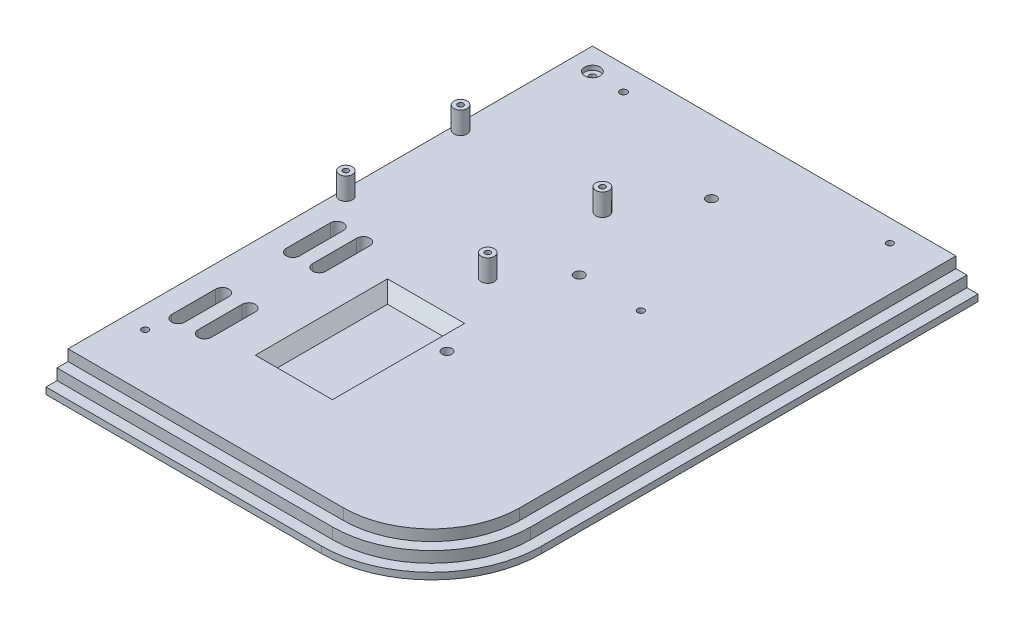
SolidWorks part; units mm, degrees
material "PETG"
ref_plane "Alzado" through (0, 0, 0) normal (0, 0, 1) x (1, 0, 0)
ref_plane "Planta" through (0, 0, 0) normal (0, 1, 0) x (1, 0, 0)
ref_plane "Vista lateral" through (0, 0, 0) normal (1, 0, 0) x (0, 0, -1)
sketch "Croquis1" plane through (0, 0, 0) normal (0, 1, 0) x (1, 0, 0)
  line L1 (125, 225) -> (-125, 225)
  line L2 (175, 175) -> (175, -175)
  line L3 (125, -225) -> (-125, -225)
  line L4 (-175, 175) -> (-175, -175)
  line L5 (175, 225) -> (-175, -225) construction
  line L6 (175, -225) -> (-175, 225) construction
  arc A0 (-125, -225) -> (-175, -175) centre (-125, -175) cw
  arc A1 (175, -175) -> (125, -225) centre (125, -175) cw
  arc A2 (125, 225) -> (175, 175) centre (125, 175) cw
  arc A3 (-125, 225) -> (-175, 175) centre (-125, 175) ccw
  point P0 (0, 0)
  dimension "D3" = 50
  dimension "D1" = 450
  dimension "D2" = 350
extrude "Saliente-Extruir1" add sketch "Croquis1" along normal blind 3
sketch "Croquis2" plane through (0, 3, 0) normal (0, 1, 0) x (1, 0, 0)
  line L8 (-125, -220) -> (125, -220)
  line L9 (170, -175) -> (170, 175)
  line L10 (125, 220) -> (-125, 220)
  line L11 (-170, 175) -> (-170, -175)
  line L12 (-125, -220) -> (125, -220)
  line L13 (170, -175) -> (170, 175)
  line L14 (125, 220) -> (-125, 220)
  line L15 (-170, 175) -> (-170, -175)
  arc A8 (-170, -175) -> (-125, -220) centre (-125, -175) ccw
  arc A9 (125, -220) -> (170, -175) centre (125, -175) ccw
  arc A10 (170, 175) -> (125, 220) centre (125, 175) ccw
  arc A11 (-125, 220) -> (-170, 175) centre (-125, 175) ccw
  arc A12 (-170, -175) -> (-125, -220) centre (-125, -175) ccw
  arc A13 (125, -220) -> (170, -175) centre (125, -175) ccw
  arc A14 (170, 175) -> (125, 220) centre (125, 175) ccw
  arc A15 (-125, 220) -> (-170, 175) centre (-125, 175) ccw
  dimension "D1" = 5
extrude "Saliente-Extruir2" add sketch "Croquis2" along normal blind 5
sketch "Croquis3" plane through (0, 8, 0) normal (0, 1, 0) x (1, 0, 0)
  line L8 (-125, -215) -> (125, -215)
  line L9 (165, -175) -> (165, 175)
  line L10 (125, 215) -> (-125, 215)
  line L11 (-165, 175) -> (-165, -175)
  line L12 (-125, -215) -> (125, -215)
  line L13 (165, -175) -> (165, 175)
  line L14 (125, 215) -> (-125, 215)
  line L15 (-165, 175) -> (-165, -175)
  arc A8 (-165, -175) -> (-125, -215) centre (-125, -175) ccw
  arc A9 (125, -215) -> (165, -175) centre (125, -175) ccw
  arc A10 (165, 175) -> (125, 215) centre (125, 175) ccw
  arc A11 (-125, 215) -> (-165, 175) centre (-125, 175) ccw
  arc A12 (-165, -175) -> (-125, -215) centre (-125, -175) ccw
  arc A13 (125, -215) -> (165, -175) centre (125, -175) ccw
  arc A14 (165, 175) -> (125, 215) centre (125, 175) ccw
  arc A15 (-125, 215) -> (-165, 175) centre (-125, 175) ccw
  dimension "D1" = 5
extrude "Saliente-Extruir3" add sketch "Croquis3" along normal blind 5
sketch "Croquis6" plane through (0, 13, 0) normal (0, 1, 0) x (1, 0, 0)
  line L0 (0, 0) -> (0, -215) construction
  line L1 (-125, -215) -> (125, -215) construction
  circle A0 centre (-87, -130) radius 2.25
  circle A1 centre (-87, -70) radius 2.25
  circle A2 centre (-87, -10) radius 2.25
  circle A3 centre (87, -130) radius 2.25
  circle A4 centre (87, -70) radius 2.25
  circle A5 centre (87, -10) radius 2.25
  dimension "D1" = 4.5
  dimension "D2" = 4.5
  dimension "D3" = 4.5
  dimension "D4" = 87
  dimension "D5" = 60
  dimension "D6" = 60
  dimension "D7" = 10
extrude "Cortar-Extruir3" cut sketch "Croquis6" against normal blind 5
sketch "Croquis7" plane through (0, 13, 0) normal (0, 1, 0) x (1, 0, 0)
  line L0 (0, -11.4875) -> (0, -220) construction
  line L1 (-125, -220) -> (125, -220) construction
  circle A0 centre (-115, -70) radius 1.5
  circle A1 centre (-115, 130) radius 1.5
  circle A2 centre (115, -70) radius 1.5
  circle A3 centre (115, 130) radius 1.5
  dimension "D1" = 3
  dimension "D2" = 3
  dimension "D3" = 115
  dimension "D4" = 70
  dimension "D5" = 130
  dimension "D6" = 115
extrude "Cortar-Extruir4" cut sketch "Croquis7" against normal through all
sketch "Croquis8" plane through (0, 13, 0) normal (0, 1, 0) x (1, 0, 0)
  line L0 (13.0147, -158) -> (13.0147, -178) construction
  line L4 (16.0147, -158) -> (16.0147, -178)
  line L5 (10.0147, -158) -> (10.0147, -178)
  line L6 (25.0147, -158) -> (25.0147, -178) construction
  line L7 (28.0147, -158) -> (28.0147, -178)
  line L8 (22.0147, -158) -> (22.0147, -178)
  line L9 (25.0147, -106) -> (25.0147, -126) construction
  line L10 (28.0147, -106) -> (28.0147, -126)
  line L11 (22.0147, -106) -> (22.0147, -126)
  line L12 (13.0147, -106) -> (13.0147, -126) construction
  line L15 (16.0147, -106) -> (16.0147, -126)
  line L16 (10.0147, -106) -> (10.0147, -126)
  arc A0 (10.0147, -168) -> (13.0147, -171) centre (13.0147, -168) ccw construction
  arc A1 (25.0147, -171) -> (28.0147, -168) centre (25.0147, -168) ccw construction
  arc A2 (16.0147, -116) -> (13.0147, -113) centre (13.0147, -116) ccw construction
  arc A3 (22.0147, -116) -> (25.0147, -119) centre (25.0147, -116) ccw construction
  arc A6 (16.0147, -158) -> (10.0147, -158) centre (13.0147, -158) ccw
  arc A7 (10.0147, -178) -> (16.0147, -178) centre (13.0147, -178) ccw
  arc A8 (28.0147, -158) -> (22.0147, -158) centre (25.0147, -158) ccw
  arc A9 (22.0147, -178) -> (28.0147, -178) centre (25.0147, -178) ccw
  arc A10 (28.0147, -106) -> (22.0147, -106) centre (25.0147, -106) ccw
  arc A11 (22.0147, -126) -> (28.0147, -126) centre (25.0147, -126) ccw
  arc A14 (16.0147, -106) -> (10.0147, -106) centre (13.0147, -106) ccw
  arc A15 (10.0147, -126) -> (16.0147, -126) centre (13.0147, -126) ccw
  arc A16 (13.0147, -113) -> (10.0147, -116) centre (13.0147, -116) ccw construction
  arc A17 (10.0147, -116) -> (13.0147, -119) centre (13.0147, -116) ccw construction
  arc A18 (13.0147, -119) -> (16.0147, -116) centre (13.0147, -116) ccw construction
  arc A19 (28.0147, -116) -> (25.0147, -113) centre (25.0147, -116) ccw construction
  arc A20 (25.0147, -119) -> (28.0147, -116) centre (25.0147, -116) ccw construction
  arc A21 (25.0147, -113) -> (22.0147, -116) centre (25.0147, -116) ccw construction
  arc A22 (25.0147, -165) -> (22.0147, -168) centre (25.0147, -168) ccw construction
  arc A23 (22.0147, -168) -> (25.0147, -171) centre (25.0147, -168) ccw construction
  arc A24 (28.0147, -168) -> (25.0147, -165) centre (25.0147, -168) ccw construction
  arc A25 (16.0147, -168) -> (13.0147, -165) centre (13.0147, -168) ccw construction
  arc A26 (13.0147, -171) -> (16.0147, -168) centre (13.0147, -168) ccw construction
  arc A27 (13.0147, -165) -> (10.0147, -168) centre (13.0147, -168) ccw construction
  point P10 (13.0147, -168)
  point P16 (25.0147, -168)
  point P23 (25.0147, -116)
  point P32 (13.0147, -116)
  dimension "D1" = 6
  dimension "D2" = 6
  dimension "D3" = 6
  dimension "D4" = 6
  dimension "D5" = 12
  dimension "D6" = 52
  dimension "D7" = 116
  dimension "D8" = 13.0147
  dimension "D9" = 20
  dimension "D10" = 20
  dimension "D11" = 20
  dimension "D12" = 20
extrude "Cortar-Extruir5" cut sketch "Croquis8" against normal blind 8
sketch "Croquis9" plane through (0, 13, 0) normal (0, 1, 0) x (1, 0, 0)
  circle A0 centre (13.0147, -168) radius 1.5
  circle A1 centre (25.0147, -168) radius 1.5
  circle A2 centre (13.0147, -116) radius 1.5
  circle A3 centre (25.0147, -116) radius 1.5
  circle A4 centre (-87, -70) radius 2.25 construction
  circle A5 centre (-87, -130) radius 1.5
  circle A6 centre (-87, -70) radius 1.5
  circle A7 centre (-87, -10) radius 1.5
  circle A8 centre (87, -10) radius 1.5
  circle A9 centre (87, -70) radius 1.5
  circle A10 centre (87, -130) radius 1.5
  dimension "D1" = 3
  dimension "D2" = 3
  dimension "D3" = 3
  dimension "D4" = 3
  dimension "D5" = 100.0147
  dimension "D6" = 112.0147
  dimension "D7" = 46
  dimension "D8" = 98
extrude "Cortar-Extruir6" cut sketch "Croquis9" against normal through all
sketch "Croquis10" plane through (0, 13, 0) normal (0, 1, 0) x (1, 0, 0)
  line L1 (50, -120) -> (75, -120)
  line L2 (50, -120) -> (50, -170)
  line L3 (50, -170) -> (75, -170)
  line L4 (75, -120) -> (75, -170)
  dimension "D1" = 50
  dimension "D2" = 25
  dimension "D3" = 120
  dimension "D4" = 50
extrude "Cortar-Extruir7" cut sketch "Croquis10" against normal blind 5
chamfer "Chaflán1" distance 5 angle 45 4 edges at (62.5, 13, 120) (50, 13, 145) (62.5, 13, 170) (75, 13, 145)
sketch "Croquis13" plane through (0, 13, 0) normal (0, 1, 0) x (1, 0, 0)
  circle A0 centre (-60, -50) radius 2.25
  circle A1 centre (-20, -50) radius 2.25
  circle A2 centre (-20, -90) radius 2.25
  circle A3 centre (-60, -90) radius 2.25
  circle A4 centre (-20, -50) radius 3.5
  circle A5 centre (-60, -50) radius 3.5
  circle A6 centre (-60, -90) radius 3.5
  circle A7 centre (-20, -90) radius 3.5
  dimension "D1" = 4.5
  dimension "D2" = 40
  dimension "D6" = 7
  dimension "D3" = 40
  dimension "D4" = 20
  dimension "D5" = 50
extrude "Saliente-Extruir4" add sketch "Croquis13" along normal blind 25
sketch "Croquis14" plane through (0, 13, 0) normal (0, 1, 0) x (1, 0, 0)
  circle A0 centre (3.15, -40) radius 1.25
  circle A1 centre (67.55, -40) radius 1.25
  circle A3 centre (67.55, -40) radius 3
  circle A4 centre (3.15, -40) radius 3
  circle A5 centre (3, -91.9) radius 3
  circle A6 centre (3, -91.9) radius 1.25
  circle A7 centre (67.4, -91.9) radius 3
  circle A8 centre (67.4, -91.9) radius 1.25
  circle A9 centre (-10, -102.9) radius 1.5
  circle A10 centre (-10, -102.9) radius 3
  circle A11 centre (-10, -118.1085) radius 3
  circle A12 centre (-10, -118.1085) radius 1.5
  dimension "D1" = 2.5
  dimension "D2" = 6
  dimension "D7" = 3
  dimension "D8" = 6
  dimension "D9" = 6
  dimension "D10" = 3
  dimension "D3" = 51.9
  dimension "D4" = 64.4
  dimension "D5" = 40
  dimension "D6" = 3
  dimension "D11" = 11
  dimension "D12" = 13
  dimension "D13" = 15.2085
  dimension "D14" = 64.4
  dimension "D15" = 0.15
extrude "Saliente-Extruir5" add sketch "Croquis14" along normal blind 10
sketch "Croquis12" plane through (0, 13, 0) normal (0, 1, 0) x (1, 0, 0)
  line L0 (-25.1, 12) -> (-25.1, 13.6) construction
  line L1 (-25.1, 12) -> (-23.5, 12) construction
  line L2 (25.1, 12) -> (23.5, 12) construction
  line L3 (25.1, 12) -> (25.1, 13.6) construction
  line L4 (25.1, 162.2) -> (25.1, 160.6) construction
  line L5 (25.1, 162.2) -> (23.5, 162.2) construction
  line L6 (-25.1, 162.2) -> (-23.5, 162.2) construction
  line L7 (-25.1, 162.2) -> (-25.1, 160.6) construction
  circle A0 centre (-25.1, 162.2) radius 1.6
  circle A1 centre (25.1, 162.2) radius 1.6
  circle A2 centre (-25.1, 12) radius 1.6
  circle A3 centre (25.1, 12) radius 1.6
  dimension "D4" = 3.2
  dimension "D1" = 12
  dimension "D2" = 47
  dimension "D3" = 23.5
  dimension "D5" = 147
  dimension "D6" = 147
extrude "Cortar-Extruir9" cut sketch "Croquis12" against normal through all
sketch "Croquis11" plane through (0, 0, 0) normal (0, -1, 0) x (1, 0, 0)
  line L0 (13.0147, 168) -> (25.0147, 168) construction
  line L1 (13.0147, 188) -> (25.0147, 188)
  line L2 (13.0147, 148) -> (25.0147, 148)
  line L3 (13.0147, 116) -> (25.0147, 116) construction
  line L4 (13.0147, 136) -> (25.0147, 136)
  line L5 (13.0147, 96) -> (25.0147, 96)
  circle A4 centre (87, 130) radius 6
  circle A5 centre (87, 70) radius 6
  circle A6 centre (87, 10) radius 6
  circle A7 centre (-87, 10) radius 6
  circle A8 centre (-87, 70) radius 6
  circle A9 centre (-87, 130) radius 6
  circle A10 centre (-115, 70) radius 6
  circle A11 centre (115, 70) radius 6
  circle A12 centre (115, -130) radius 6
  circle A15 centre (-115, -130) radius 6
  arc A16 (13.0147, 188) -> (13.0147, 148) centre (13.0147, 168) ccw
  arc A17 (25.0147, 148) -> (25.0147, 188) centre (25.0147, 168) ccw
  circle A18 centre (-25.1, -162.2) radius 6
  arc A19 (13.0147, 136) -> (13.0147, 96) centre (13.0147, 116) ccw
  arc A20 (25.0147, 96) -> (25.0147, 136) centre (25.0147, 116) ccw
  circle A21 centre (25.1, -162.2) radius 6
  circle A22 centre (-25.1, -12) radius 6
  circle A23 centre (25.1, -12) radius 6
  point P3 (19.0147, 168)
  point P10 (19.0147, 116)
  dimension "D1" = 12
  dimension "D2" = 20
  dimension "D3" = 20
extrude "Cortar-Extruir8" cut sketch "Croquis11" against normal blind 5
sketch "Croquis16" plane through (0, 0, 0) normal (1, 0, 0) x (0, 0, -1)
  line L0 (-175, 0) -> (175, 0) construction
  line L5 (-175, 8) -> (175, 8) construction
  line L6 (2, 8) -> (42, 8)
  line L7 (2, 8) -> (2, 0)
  line L8 (2, 0) -> (42, 0)
  line L9 (42, 8) -> (42, 0)
  dimension "D1" = 40
  dimension "D2" = 2
extrude "Cortar-Extruir10" cut sketch "Croquis16" against normal mid plane 40
sketch "Croquis17" plane through (0, 13, 0) normal (0, 1, 0) x (1, 0, 0)
  line L0 (-175, 23) -> (0, 23) construction
  line L2 (0, 23) -> (0, -225)
  line L3 (-125, -225) -> (125, -225) construction
  line L4 (-175, 175) -> (-175, -175) construction
  line L5 (-175, 23) -> (-175, 225)
  line L6 (-175, 225) -> (175, 225)
  line L7 (175, 225) -> (175, 23)
  line L8 (175, -225) -> (0, -225) construction
  line L9 (125, 225) -> (-125, 225) construction
  line L10 (175, -175) -> (175, 175) construction
  line L11 (0, 23) -> (175, 23)
  line L12 (-175, 23) -> (-175, -225)
  line L13 (-175, -225) -> (0, -225)
  line L14 (175, 23) -> (175, -225) construction
  dimension "D1" = 248
extrude "Cortar-Extruir11" cut sketch "Croquis17" against normal mid plane 60
sketch "Croquis19" plane through (0, 13, 0) normal (0, 1, 0) x (1, 0, 0)
  line L4 (0, 23) -> (165, 23) construction
  line L5 (175, -175) -> (175, 23) construction
  line L6 (0, -215) -> (0, -91.9) construction
  line L7 (0, -225) -> (125, -225) construction
  line L8 (0, -91.9) -> (0, 23) construction
  circle A0 centre (10, 13) radius 1.5
  circle A1 centre (10, -190) radius 1.5
  circle A2 centre (145, 13) radius 1.5
  dimension "D1" = 3
  dimension "D2" = 3
  dimension "D3" = 3
  dimension "D4" = 10
  dimension "D5" = 30
  dimension "D6" = 10
  dimension "D7" = 35
  dimension "D8" = 10
extrude "Cortar-Extruir12" cut sketch "Croquis19" against normal blind 70
sketch "Croquis20" plane through (0, 0, 0) normal (-1, 0, 0) x (0, 0, 1)
  line L5 (225, 0) -> (225, 3) construction
  line L6 (180, 7.5) -> (200, 7.5)
  line L7 (180, 7.5) -> (180, 0)
  line L8 (180, 0) -> (200, 0)
  line L9 (200, 7.5) -> (200, 0)
  line L10 (183.1861, 0) -> (225, 0) construction
  dimension "D1" = 25
  dimension "D2" = 20
  dimension "D3" = 7.5
extrude "Cortar-Extruir13" cut sketch "Croquis20" against normal blind 20
sketch "Croquis21" plane through (0, 0, -23) normal (0, 0, -1) x (-1, 0, 0)
  line L0 (-175, 0) -> (-20, 0) construction
  line L1 (-155, 7.5) -> (-135, 7.5)
  line L2 (-155, 7.5) -> (-155, 0)
  line L3 (-155, 0) -> (-135, 0)
  line L4 (-135, 7.5) -> (-135, 0)
  dimension "D1" = 7.5
  dimension "D2" = 20
  dimension "D3" = 20
extrude "Cortar-Extruir14" cut sketch "Croquis21" against normal blind 20
sketch "Croquis22" plane through (0, 0, 0) normal (0, -1, 0) x (1, 0, 0)
  line L21 (7, 5) -> (27, 5)
  line L22 (7, 5) -> (27, 5)
  line L23 (27, 5) -> (27, 0.8604)
  line L24 (27, 5) -> (27, 0.8604)
  line L36 (168, -16) -> (168, 175)
  line L37 (125, 218) -> (7, 218)
  line L38 (27, 207) -> (27, 194.9269)
  line L39 (25.0147, 89) -> (13.0147, 89)
  line L40 (7, 89.6785) -> (7, 5)
  line L43 (37.4693, -16) -> (128, -16)
  line L44 (128, -16) -> (128, 4)
  line L45 (128, 4) -> (162, 4)
  line L46 (168, -16) -> (168, 175)
  line L47 (125, 218) -> (7, 218)
  line L48 (27, 207) -> (27, 194.9269)
  line L49 (25.0147, 89) -> (13.0147, 89)
  line L50 (7, 89.6785) -> (7, 5)
  line L53 (37.4693, -16) -> (128, -16)
  line L54 (128, -16) -> (128, 4)
  line L55 (128, 4) -> (162, 4)
  line L56 (162, 4) -> (162, -16)
  line L57 (162, 4) -> (162, -16)
  line L58 (162, -16) -> (168, -16)
  line L59 (162, -16) -> (168, -16)
  line L60 (7, 218) -> (7, 207)
  line L61 (7, 218) -> (7, 207)
  line L62 (7, 207) -> (27, 207)
  line L66 (7, 207) -> (27, 207)
  arc A7 (37.4693, -16) -> (27, 0.8604) centre (25.1, -12) ccw
  circle A8 centre (87, 130) radius 26
  circle A9 centre (87, 130) radius 26
  arc A10 (37.4693, -16) -> (27, 0.8604) centre (25.1, -12) ccw
  circle A11 centre (87, 70) radius 26
  arc A12 (168, 175) -> (125, 218) centre (125, 175) ccw
  arc A13 (32.2948, 142) -> (27, 194.9269) centre (25.0147, 168) ccw
  arc A14 (25.0147, 89) -> (32.2948, 142) centre (25.0147, 116) ccw
  arc A15 (7, 89.6785) -> (13.0147, 89) centre (13.0147, 116) ccw
  arc A16 (168, 175) -> (125, 218) centre (125, 175) ccw
  arc A17 (32.2948, 142) -> (27, 194.9269) centre (25.0147, 168) ccw
  arc A18 (25.0147, 89) -> (32.2948, 142) centre (25.0147, 116) ccw
  arc A19 (7, 89.6785) -> (13.0147, 89) centre (13.0147, 116) ccw
  arc A20 (108.5, 84.6202) -> (108.5, 55.3798) centre (87, 70) ccw
  circle A22 centre (87, 10) radius 25
  circle A23 centre (87, 10) radius 25
  circle A25 centre (115, 70) radius 16
  arc A26 (108.5, 55.3798) -> (108.5, 84.6202) centre (115, 70) ccw
  arc A27 (108.5, 84.6202) -> (108.5, 55.3798) centre (115, 70) ccw construction
  arc A30 (108.5, 55.3798) -> (108.5, 84.6202) centre (87, 70) ccw construction
  dimension "D1" = 7
  dimension "D2" = 20
  dimension "D3" = 20
  dimension "D4" = 19
  dimension "D5" = 10
extrude "Cortar-Extruir15" cut sketch "Croquis22" against normal blind 6 contours L57 L59 L46 A16 L47 L61 L66 L48 A17 A18 L49 A19 L50 L22 L24 A10 L53 L54 L55 | A9 | A20 A26 | A23
sketch "Croquis23" plane through (0, 13, 0) normal (0, 1, 0) x (1, 0, 0)
  circle A2 centre (10, 13) radius 3.5
  circle A3 centre (10, 13) radius 3.5
  dimension "D1" = 2
extrude "Cortar-Extruir16" cut sketch "Croquis23" against normal blind 2
